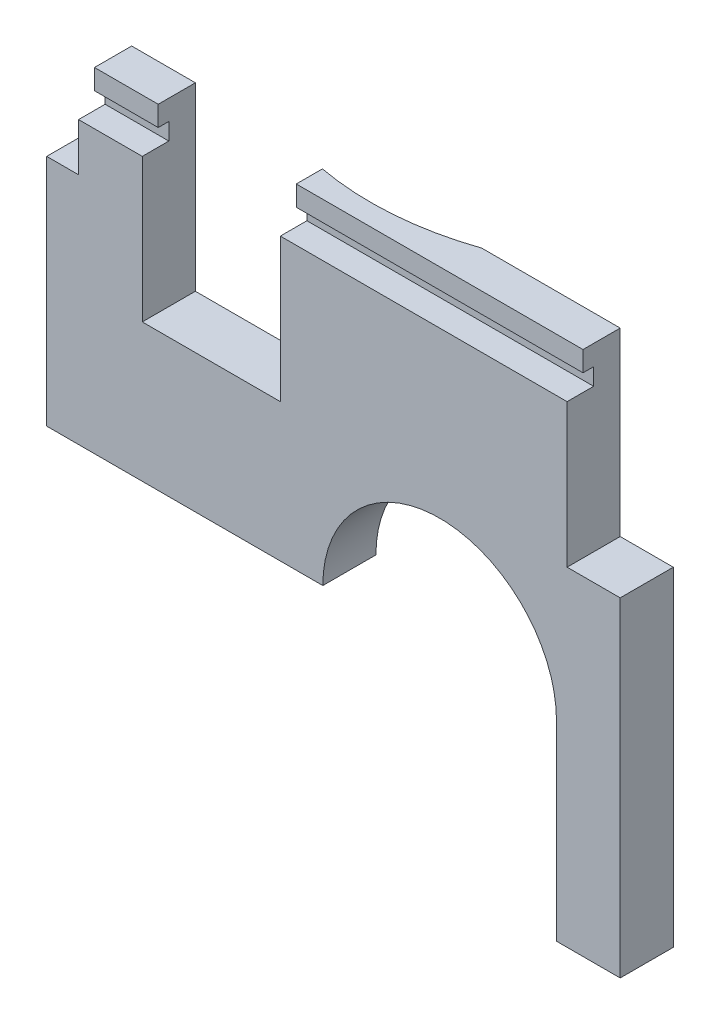
SolidWorks part; units mm, degrees
note: '?' marks a value the reader was unsure of.
ref_plane "Спереди" through (0, 0, 0) normal (0, 0, 1) x (1, 0, 0)
ref_plane "Сверху" through (0, 0, 0) normal (0, 1, 0) x (1, 0, 0)
ref_plane "Справа" through (0, 0, 0) normal (1, 0, 0) x (0, 0, -1)
sketch "Эскиз1" plane through (0, 0, 0) normal (0, 0, 1) x (1, 0, 0)
  line L1 (0, 0) -> (54, 0)
  line L2 (0, 0) -> (0, 48)
  line L3 (0, 48) -> (54, 48)
  line L4 (54, 0) -> (54, 48)
  dimension "D1" = 54
  dimension "D2" = 48
extrude "Бобышка-Вытянуть1" add sketch "Эскиз1" along normal blind 5
sketch "Эскиз3" plane through (0, 0, 5) normal (0, 0, 1) x (1, 0, 0)
  line L0 (0, 40) -> (3, 40)
  line L1 (0, 48) -> (0, 0) construction
  line L2 (3, 40) -> (3, 48)
  line L3 (54, 48) -> (0, 48) construction
  line L4 (3, 48) -> (9, 48)
  line L5 (9, 48) -> (9, 31)
  line L6 (9, 31) -> (22, 31)
  line L7 (22, 31) -> (22, 48)
  line L8 (22, 48) -> (49, 48)
  line L9 (49, 48) -> (49, 31)
  line L10 (49, 31) -> (54, 31)
  line L11 (54, 0) -> (54, 48) construction
  line L12 (0, 0) -> (54, 0) construction
  line M1 (0, 48) -> (0, 0)
  line M3 (54, 0) -> (54, 48)
  line M4 (54, 48) -> (0, 48)
  dimension "D1" = 40
  dimension "D2" = 31
  dimension "D3" = 3
  dimension "D4" = 6
  dimension "D5" = 13
  dimension "D6" = 49
  dimension "D7" = 31
extrude "Вырез-Вытянуть1" cut sketch "Эскиз3" against normal through all contours L0 L2 M4 M1 | L6 L7 L5 M4 | L9 L10 M3 M4
sketch "Эскиз4" plane through (0, 0, 0) normal (-1, 0, 0) x (0, 0, 1)
  line L0 (3.5, 48) -> (3.5, 46.1)
  line L1 (0, 48) -> (5, 48) construction
  line L2 (3.5, 46.1) -> (2.5, 46.1)
  line L3 (2.5, 46.1) -> (2.5, 44.5)
  line L5 (2.5, 44.5) -> (5, 44.5)
  line L6 (5, 40) -> (5, 48) construction
  line L7 (5, 0) -> (0, 0) construction
  dimension "D1" = 1.6
  dimension "D2" = 44.5
  dimension "D3" = 2.5
  dimension "D4" = 1.5
extrude "Вырез-Вытянуть2" cut sketch "Эскиз4" against normal through all
sketch "Эскиз5" plane through (0, 0, 5) normal (0, 0, 1) x (1, 0, 0)
  line L0 (48, 0) -> (48, 18)
  line L1 (0, 0) -> (54, 0) construction
  line L2 (26, 18) -> (0, 18)
  line L3 (0, 40) -> (0, 0) construction
  arc A0 (48, 18) -> (26, 18) centre (37, 18) ccw
  dimension "D3" = 18
  dimension "D1" = 11
  dimension "D2" = 37
  dimension "D4" = 18
extrude "Вырез-Вытянуть3" cut sketch "Эскиз5" against normal through all
sketch "Эскиз6" plane through (0, 48, 0) normal (0, 1, 0) x (1, 0, 0)
  line L0 (49, 0) -> (22, 0) construction
  line L1 (0, 0) -> (0, -5) construction
  circle A0 centre (27, 26) radius 27.5
  line M3 (49, 0) -> (22, 0)
  dimension "D1" = 55
  dimension "D2" = 26
  dimension "D3" = 27
extrude "Вырез-Вытянуть4" cut sketch "Эскиз6" against normal blind 12 contours A0 M3
hole_wizard "Отверстие обработанное метчиком M31" positions "Трехмерный эскиз1" profile "Эскиз7" tap size "M3" standard "DIN"
sketch3d "Трехмерный эскиз1"
  line L1 (0, 0, 5) -> (0, 0, 0) construction
  line L2 (0, 40, 5) -> (0, 18, 5) construction
  line L3 (48, 0, 5) -> (54, 0, 5) construction
  point P0 (0, 22, 2.5)
  point P2 (0, 34, 2.5)
  point P4 (51, 0, 2.5)
  dimension "D1" = 51
  dimension "D2" = 22
  dimension "D3" = 34
  dimension "D4" = 2.5
  dimension "D5" = 2.5
  dimension "D6" = 2.5
cosmetic thread "Отверстие резьбы1" parameters "D1"=7.5, "D2"=3
cosmetic thread "Отверстие резьбы2" parameters "D1"=7.5, "D2"=3
cosmetic thread "Отверстие резьбы3" parameters "D1"=6.4388, "D2"=3
sketch "Эскиз7" plane through (0, 22, 2.5) normal (0, 1, 0) x (0, 0, 1)
  line L0 (0, 0) -> (0, 8.2511)
  line L1 (0, 8.2511) -> (1.25, 7.5)
  line L2 (1.25, 7.5) -> (1.25, 0.2451)
  line L3 (1.25, 0.2451) -> (1.6, 0)
  line L5 (1.6, 0) -> (0, 0)
  line L6 (-1.25, 0.2451) -> (-1.6, 0) construction
  line L10 (0, 8.2511) -> (-1.25, 7.5) construction
  line L11 (0, -6.35) -> (0, 107.95) construction
  dimension "Диаметр сверла" = 2.5
  dimension "Глубина сверла" = 7.5
  dimension "Диаметр передней зенковки" = 3.2
  dimension "Угол передней зенковки" = 110
  dimension "Угол заточки сверла" = 118
chamfer "Фаска2" [suppressed] distance 4 angle 30
sketch "Эскиз8" plane through (0, 0, 0) normal (0, -1, 0) x (1, 0, 0)
  line L0 (38.4606, 5) -> (49.1831, 0)
  line L2 (48, 0) -> (54, 0) construction
  line L3 (49.1831, 0) -> (38.4606, 0)
  line L4 (38.4606, 0) -> (38.4606, 5)
  line L5 (48, 5) -> (26, 5) construction
  dimension "D1" = 25
  dimension "D2" = 0.5
extrude "Вырез-Вытянуть5" [suppressed] cut sketch "Эскиз8" against normal blind 15
sketch "Эскиз9" [suppressed] plane through (8.7844, 0, 18.8382) normal (-0.4226, 0, -0.9063) x (-0.9063, 0, 0.4226)
  line L0 (-41.3897, 0) -> (-41.3897, 18) construction
  line L1 (-44.575, 0) -> (-48.9406, 0) construction
  circle A0 centre (-36.3897, 18) radius 10
  dimension "D1" = 20
  dimension "D2" = 5
  dimension "D3" = 18
extrude "Вырез-Вытянуть6" [suppressed] cut sketch "Эскиз9" against normal through all and the other way through all
chamfer "Фаска3" [suppressed] distance 2 angle 45
ref_axis "Ось1" through (37, 18, 0) along (0, 0, 1)?
ref_plane "Плоскость1" through (1.4558, -2.5215, 0) normal (-0.5, 0.866, 0) x (0, 0, -1)
sketch "Эскиз10" plane through (1.4558, -2.5215, 0) normal (-0.5, 0.866, 0) x (0, 0, -1)
  line L0 (-5.3065, -46.0429) -> (3.8896, -46.0429) construction
  line L1 (-6.0829, -46.0429) -> (2, -60.0429)
  line L2 (2, -60.0429) -> (2, -46.0429)
  line L3 (2, -46.0429) -> (-6.0829, -46.0429)
  line L4 (0, -66.4352) -> (0, -55.1407) construction
  line L5 (0, -41.0429) -> (-5, -41.0429) construction
  dimension "D1" = 7
  dimension "D2" = 2
  dimension "D3" = 60
  dimension "D4" = 5
revolve "Вырез-Повернуть1" cut sketch "Эскиз10" angle 360 about L0
